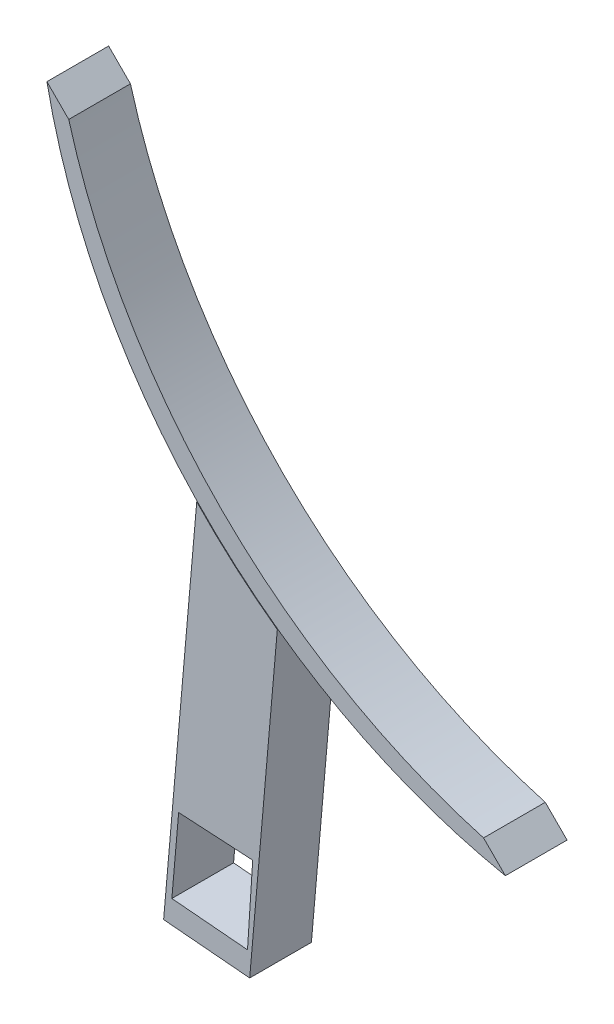
SolidWorks part; units mm, degrees
ref_plane "Front Plane" through (0, 0, 0) normal (0, 0, 1) x (1, 0, 0)
ref_plane "Top Plane" through (0, 0, 0) normal (0, 1, 0) x (1, 0, 0)
ref_plane "Right Plane" through (0, 0, 0) normal (1, 0, 0) x (0, 0, -1)
sketch "Sketch1" plane through (0, 0, 0) normal (0, 0, 1) x (1, 0, 0)
  line L0 (40.9843, -16.2773) -> (37.4488, -12.7418)
  line L1 (-33.3023, 58.0093) -> (-29.7668, 54.4738)
  arc A0 (40.9843, -16.2773) -> (-33.3023, 58.0093) centre (59.7952, 76.8202) cw
  arc A1 (37.4488, -12.7418) -> (-29.7668, 54.4738) centre (63.5695, 80.5945) cw
extrude "Boss-Extrude1" add sketch "Sketch1" along normal blind 10
scale "Scale1" bodies to scale 101 scale about centroid uniform scaling yes scale factor 0.5
ref_plane "Plane5" through (0.1123, 1.284, 0) normal (0.0872, 0.9962, 0) x (0, 0, -1)
sketch "Sketch4" plane through (7.0102, 0.6805, -0.2582) normal (0.0872, 0.9962, 0) x (0, 0, -1)
  line L1 (-2.8017, 13.9898) -> (-7.8017, 13.9898)
  line L2 (-2.8017, 13.9898) -> (-2.8017, 6.9898)
  line L3 (-2.8017, 6.9898) -> (-7.8017, 6.9898)
  line L4 (-7.8017, 13.9898) -> (-7.8017, 6.9898)
  dimension "D1" = 7
  dimension "D2" = 5
extrude "Boss-Extrude2" add sketch "Sketch4" along normal up to surface and the other way blind 20 up to face at (-2.3987, 14.6264, 5)
ref_plane "Plane6" through (-5.9875, 12.6311, 7.5435) normal (0, 0, 1) x (1, 0, 0)
sketch "Sketch10" plane through (0, 0, 7.5435) normal (0, 0, 1) x (1, 0, 0)
  line L1 (-8.004, -16.2091) -> (-7.452, -9.8995)
  line L2 (-8.004, -16.2091) -> (-1.8744, -16.7453)
  line L3 (-1.8744, -16.7453) -> (-1.452, -10.2453)
  line L4 (-7.452, -9.8995) -> (-1.452, -10.2453)
  dimension "D1" = 6
  dimension "D2" = 6.5
extrude "Cut-Extrude1" cut sketch "Sketch10" against normal through all contours L2 L1 L4 L3
